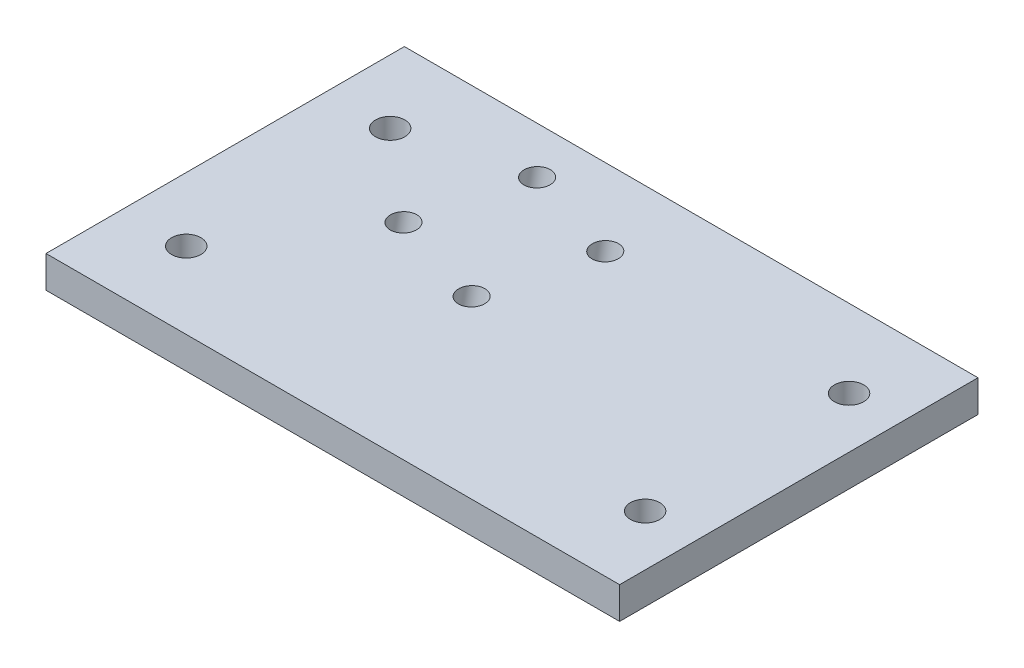
SolidWorks part; units mm, degrees
ref_plane "Front" through (0, 0, 0) normal (0, 0, 1) x (1, 0, 0)
ref_plane "Top" through (0, 0, 0) normal (0, 1, 0) x (1, 0, 0)
ref_plane "Right" through (0, 0, 0) normal (1, 0, 0) x (0, 0, -1)
sketch "Sketch1" plane through (0, 0, 0) normal (0, 1, 0) x (1, 0, 0)
  line L1 (0, 0) -> (90, 0)
  line L2 (0, 0) -> (0, 56.23)
  line L3 (0, 56.23) -> (90, 56.23)
  line L4 (90, 0) -> (90, 56.23)
  dimension "D1" = 90
  dimension "D2" = 56.23
extrude "Boss-Extrude1" add sketch "Sketch1" along normal blind 5
sketch "Sketch2" plane through (0, 5, 0) normal (0, 1, 0) x (1, 0, 0)
  circle A0 centre (82, 12) radius 2.3
  circle A1 centre (10, 12) radius 2.3
extrude "Cut-Extrude1" cut sketch "Sketch2" against normal blind 15
sketch "Sketch4" plane through (0, 5, 0) normal (0, 1, 0) x (1, 0, 0)
  circle A0 centre (39.2121, 27.5705) radius 2.204
  circle A1 centre (23.8176, 32.2728) radius 4.0674
  circle A2 centre (43.572, 44.174) radius 17.6111
  circle A3 centre (28.1775, 48.8763) radius 2.2
ref_plane "Plane1" through (0, 15.35, -2.9837) normal (0, 0.9816, -0.1908) x (-1, 0, 0)
sketch "Sketch6" plane through (0, 15.35, -2.9837) normal (0, 0.9816, -0.1908) x (-1, 0, 0)
  circle A0 centre (-28.1775, -47.0243) radius 2.0398
  circle A1 centre (-23.8176, -30.7258) radius 2.0398
  circle A2 centre (-39.2121, -26.1099) radius 2.0398
  circle A3 centre (-43.572, -42.4084) radius 2.0398
extrude "Cut-Extrude2" cut sketch "Sketch6" against normal blind 45
sketch "Sketch7" plane through (0, 5, 0) normal (0, 1, 0) x (1, 0, 0)
  circle A0 centre (82, 44) radius 2.3
  circle A1 centre (10, 44) radius 2.3
extrude "Cut-Extrude3" cut sketch "Sketch7" against normal blind 45
